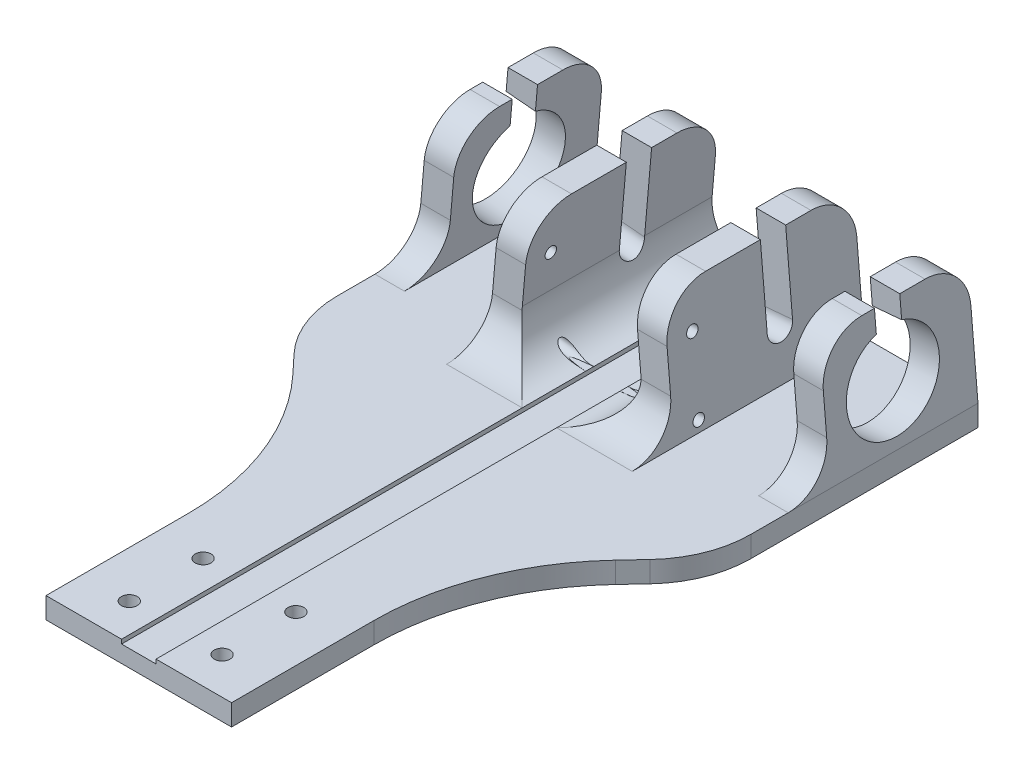
SolidWorks part; units mm, degrees
ref_plane "Front Plane" through (0, 0, 0) normal (0, 0, 1) x (1, 0, 0)
ref_plane "Top Plane" through (0, 0, 0) normal (0, 1, 0) x (1, 0, 0)
ref_plane "Right Plane" through (0, 0, 0) normal (1, 0, 0) x (0, 0, -1)
sketch "Sketch1" plane through (0, 0, 0) normal (0, 1, 0) x (1, 0, 0)
  line L1 (-24.5, 75) -> (24.5, 75)
  line L2 (-24.5, 75) -> (-24.5, -75)
  line L3 (-24.5, -75) -> (24.5, -75)
  line L4 (24.5, 75) -> (24.5, -75)
  line L5 (-24.5, 75) -> (24.5, -75) construction
  line L6 (-24.5, -75) -> (24.5, 75) construction
  point P0 (0, 0)
  dimension "D1" = 150
  dimension "D2" = 49
extrude "Boss-Extrude1" add sketch "Sketch1" along normal blind 5
sketch "Sketch2" plane through (0, 0, -75) normal (0, 0, -1) x (-1, 0, 0)
  line L0 (24.5, 5) -> (21.9443, 34.2116)
  line L1 (21.9443, 34.2116) -> (14.9443, 34.2116)
  line L2 (14.9443, 34.2116) -> (17.5, 5)
  line L3 (-24.5, 5) -> (24.5, 5) construction
  line L4 (24.5, 5) -> (24.5, 0) construction
  line L5 (17.5, 5) -> (24.5, 5)
  dimension "D1" = 7
  dimension "D2" = 5
extrude "Boss-Extrude2" add sketch "Sketch2" against normal blind 60
sketch "Sketch3" plane through (0, 0, -75) normal (0, 0, -1) x (-1, 0, 0)
  line L0 (-2.5, 5) -> (-5.1067, 34.7952)
  line L1 (-24.5, 5) -> (17.5, 5) construction
  line L2 (-5.1067, 34.7952) -> (-12.1067, 34.7952)
  line L3 (-12.1067, 34.7952) -> (-9.5, 5)
  line L4 (-9.5, 5) -> (-2.5, 5)
  line L5 (24.5, 5) -> (24.5, 0) construction
  dimension "D1" = 7
  dimension "D2" = 20
  dimension "D3" = 5
extrude "Boss-Extrude3" add sketch "Sketch3" against normal blind 70
sketch "Sketch5" plane through (-24.748, 2.1652, 0) normal (-0.9962, 0.0872, 0) x (0, 0, 1)
  line L0 (-15, 2.8457) -> (-15, 32.1689) construction
  line L1 (-34, 27.0226) -> (-34, 35.1079)
  line L2 (-5, 35.1079) -> (-75, 35.1079) construction
  line L3 (-34, 35.1079) -> (-28, 35.1079)
  line L4 (-28, 35.1079) -> (-28, 27.0226)
  arc A0 (-34, 27.0226) -> (-28, 27.0226) centre (-31, 16.4396) ccw
  dimension "D1" = 22
  dimension "D2" = 16
extrude "Cut-Extrude1" cut sketch "Sketch5" against normal blind 7
sketch "Sketch6" plane through (2.0469, -0.1791, 0) normal (-0.9962, 0.0872, 0) x (0, 0, 1)
  line L0 (-34, 16.4396) -> (-34, 35.718)
  line L1 (-5, 35.718) -> (-75, 35.718) construction
  line L2 (-34, 35.718) -> (-28, 35.718)
  line L3 (-28, 35.718) -> (-28, 16.4396)
  line L4 (-31, 27.4396) -> (-11, 27.4396) construction
  line L5 (-11, 27.4396) -> (-11, 25.1896) construction
  line L6 (-31, 16.4396) -> (-7.2102, 16.4396) construction
  arc A0 (-34, 16.4396) -> (-28, 16.4396) centre (-31, 16.4396) ccw
  circle A1 centre (-31, 16.4396) radius 11 construction
  circle A2 centre (-11, 25.1896) radius 1.35
  circle A3 centre (-11, 7.6896) radius 1.35
  dimension "D1" = 20
  dimension "D3" = 3
  dimension "D4" = 2.7
  dimension "D2" = 2.25
extrude "Cut-Extrude2" cut sketch "Sketch6" against normal blind 7
mirror "Mirror1" about plane through (24.5, 5, -75) normal (-1, 0, 0) of bodies 105
sketch "Sketch7" plane through (73.5, 0, 0) normal (1, 0, 0) x (0, 0, -1)
  line L1 (75, 5) -> (50, 5)
  line L2 (75, 5) -> (75, 45)
  line L3 (75, 45) -> (50, 45)
  line L4 (50, 5) -> (50, 45)
  line L5 (50, 5) -> (75, 5)
  line L6 (50, 5) -> (50, 0)
  line L7 (50, 0) -> (75, 0)
  line L8 (75, 5) -> (75, 0)
  line M5 (-75, 0) -> (75, 0)
  line M6 (75, 0) -> (75, 5)
  line M7 (75, 5) -> (15, 5)
  dimension "D1" = 25
  dimension "D2" = 40
extrude "Cut-Extrude3" cut sketch "Sketch7" against normal through all both and the other way through all contours L4 L2 L3 M7 | L6 M7 M5 M6 region at (73.5, 2.5, -62.5) region at (73.5, 25, -62.5)
sketch "Sketch8" plane through (73.5, 0, 0) normal (1, 0, 0) x (0, 0, -1)
  line L1 (-75, 5) -> (-100, 5)
  line L2 (-75, 5) -> (-75, 0)
  line L3 (-75, 0) -> (-100, 0)
  line L4 (-100, 5) -> (-100, 0)
  dimension "D1" = 25
extrude "Boss-Extrude4" add sketch "Sketch8" against normal up to surface (98 mm away) up to face at (-24.5, 3, 7)
sketch "Sketch9" plane through (0, 5, 0) normal (0, 1, 0) x (1, 0, 0)
  line L0 (-24.5, -42.5) -> (-24.5, 15) construction
  line L1 (-24.5, 15) -> (-24.5, -100) construction
  line L2 (-24.5, -13.75) -> (-24.5, -42.5) construction
  line L4 (-17.7236, -20.9656) -> (-13.7634, -25.1825)
  line L5 (2.5, -66.2569) -> (2.5, -100)
  line L6 (-24.5, -100) -> (73.5, -100) construction
  line L7 (2.5, -100) -> (46.5, -100)
  line L8 (46.5, -100) -> (46.5, -66.2569)
  line L9 (62.7634, -25.1825) -> (66.7236, -20.9656)
  line L10 (73.5, 15) -> (73.5, -100) construction
  line L11 (-24.5, -3.8513) -> (-24.5, 50)
  line L12 (-24.5, 50) -> (73.5, 50)
  line L13 (73.5, 50) -> (73.5, -3.8513)
  arc A0 (46.5, -66.2569) -> (62.7634, -25.1825) centre (106.5, -66.2569) cw
  arc A1 (-13.7634, -25.1825) -> (2.5, -66.2569) centre (-57.5, -66.2569) cw
  arc A2 (66.7236, -20.9656) -> (73.5, -3.8513) centre (48.5, -3.8513) ccw
  arc A3 (-24.5, -3.8513) -> (-17.7236, -20.9656) centre (0.5, -3.8513) ccw
  point P26 (73.5, -13.75)
  dimension "D1" = 60
  dimension "D2" = 25
extrude "Cut-Extrude4" cut sketch "Sketch9" against normal through all both and the other way through all flip side to cut
fillet "Fillet1" radius 10 2 edges at (9.5, 5, -27.5) (39.5, 5, -27.5)
fillet "Fillet2" radius 10 12 edges at (70, 5, -15) (37.5435, 5, -5) (11.4565, 5, -5) (-21, 5, -15) (67.4443, 34.2116, -15) (40.3933, 34.7952, -5) (8.6067, 34.7952, -5) (-18.4443, 34.2116, -15) (67.4443, 34.2116, -50) (40.3933, 34.7952, -50) (8.6067, 34.7952, -50) (-18.4443, 34.2116, -50)
sketch "Sketch10" plane through (0, 0, 0) normal (0, -1, 0) x (1, 0, 0)
  line L0 (2.5, 100) -> (2.5, 65) construction
  line L1 (2.5, 65) -> (46.5, 100) construction
  line L2 (24.5, 82.5) -> (2.5, 82.5) construction
  line L3 (2.5, 100) -> (24.5, 82.5) construction
  line L4 (24.5, 82.5) -> (24.5, 100) construction
  line L5 (2.5, 100) -> (46.5, 100) construction
  circle A0 centre (13.5, 91.25) radius 1.875
  circle A1 centre (13.5, 73.75) radius 1.875
  circle A2 centre (35.5, 73.75) radius 1.875
  circle A3 centre (35.5, 91.25) radius 1.875
  dimension "D2" = 3.75
  dimension "D1" = 35
extrude "Cut-Extrude5" cut sketch "Sketch10" against normal through all both and the other way through all
sketch "Sketch11" plane through (0, 5, 0) normal (0, 1, 0) x (1, 0, 0)
  line L0 (2.5, -100) -> (46.5, -100) construction
  line L1 (20.4131, -100) -> (28.5869, -100)
  line L2 (24.5, -100) -> (24.5, 50)
  line L3 (20.4131, 50) -> (28.5869, 50)
  line L4 (28.5869, -100) -> (28.5869, 50)
  line L5 (20.4131, -100) -> (20.4131, 50)
  line L7 (28.5869, 50) -> (20.4131, 50) construction
  line M32 (2.5, -100) -> (46.5, -100)
  dimension "D1" = 0
extrude "Cut-Extrude6" cut sketch "Sketch11" against normal blind 1 contours L5 L2 L3 M32 | L1 L4 L3 L2 region at (22.4565, 5, 25) region at (26.5435, 5, 25)
